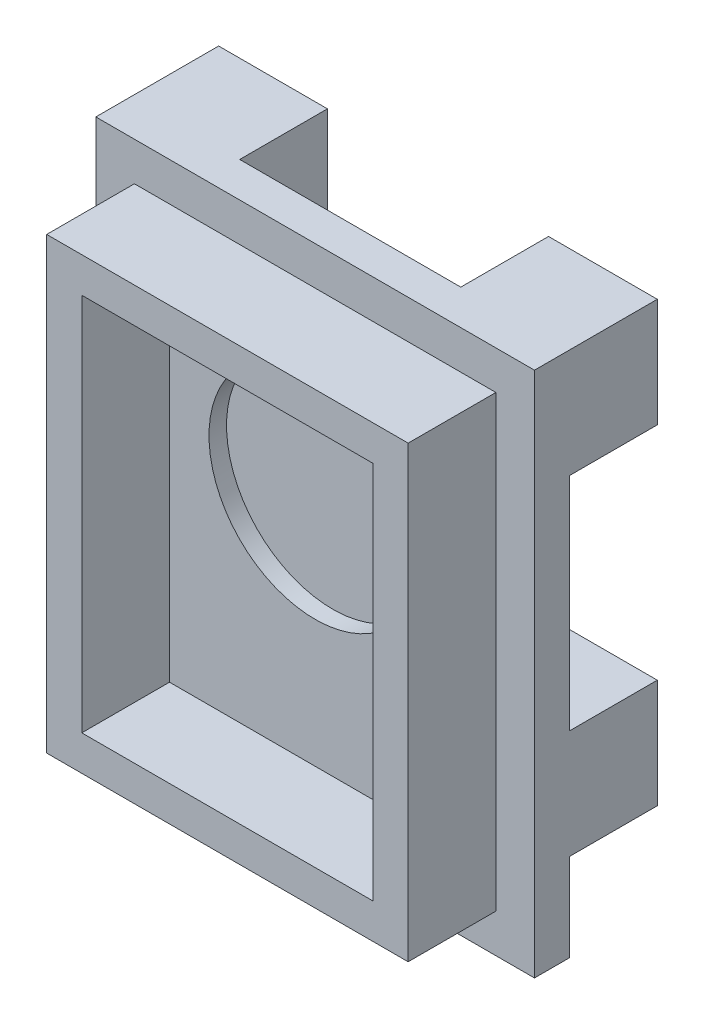
SolidWorks part; units mm, degrees
ref_plane "正面" through (0, 0, 0) normal (0, 0, 1) x (1, 0, 0)
ref_plane "平面" through (0, 0, 0) normal (0, 1, 0) x (1, 0, 0)
ref_plane "右側面" through (0, 0, 0) normal (1, 0, 0) x (0, 0, -1)
sketch "ｽｹｯﾁ1" plane through (0, 0, 0) normal (0, 0, 1) x (1, 0, 0)
  line L1 (-36.7373, 39.7071) -> (-11.7373, 39.7071)
  line L2 (-36.7373, 39.7071) -> (-36.7373, 9.7071)
  line L3 (-36.7373, 9.7071) -> (-11.7373, 9.7071)
  line L4 (-11.7373, 39.7071) -> (-11.7373, 9.7071)
  dimension "D3" = 25
  dimension "D4" = 30
extrude "ﾎﾞｽ - 押し出し1" add sketch "ｽｹｯﾁ1" along normal blind 2
sketch "ｽｹｯﾁ2" plane through (0, 0, 2) normal (0, 0, 1) x (1, 0, 0)
  line L0 (-11.7373, 39.7071) -> (-36.7373, 39.7071) construction
  line L1 (-13.9373, 37.5071) -> (-34.5373, 37.5071)
  line L2 (-13.9373, 37.5071) -> (-13.9373, 11.9071)
  line L3 (-13.9373, 11.9071) -> (-34.5373, 11.9071)
  line L4 (-34.5373, 37.5071) -> (-34.5373, 11.9071)
  line L5 (-36.7373, 9.7071) -> (-11.7373, 9.7071) construction
  line L6 (-36.7373, 39.7071) -> (-36.7373, 9.7071) construction
  line L7 (-11.7373, 9.7071) -> (-11.7373, 39.7071) construction
  dimension "D2" = 2.2
  dimension "D3" = 2.2
  dimension "D4" = 2.2
  dimension "D5" = 2.2
extrude "ﾎﾞｽ - 押し出し2" add sketch "ｽｹｯﾁ2" along normal blind 5
sketch "ｽｹｯﾁ3" plane through (0, 0, 7) normal (0, 0, 1) x (1, 0, 0)
  line L0 (-13.9373, 37.5071) -> (-34.5373, 37.5071) construction
  line L1 (-32.5373, 13.9071) -> (-15.9373, 13.9071)
  line L2 (-32.5373, 13.9071) -> (-32.5373, 35.5071)
  line L3 (-32.5373, 35.5071) -> (-15.9373, 35.5071)
  line L4 (-15.9373, 13.9071) -> (-15.9373, 35.5071)
  line L5 (-34.5373, 11.9071) -> (-13.9373, 11.9071) construction
  line L6 (-13.9373, 11.9071) -> (-13.9373, 37.5071) construction
  line L7 (-34.5373, 37.5071) -> (-34.5373, 11.9071) construction
  dimension "D1" = 21.6
  dimension "D2" = 16.6
  dimension "D3" = 2
  dimension "D4" = 2
  dimension "D5" = 2
  dimension "D6" = 2
extrude "ｶｯﾄ - 押し出し1" cut sketch "ｽｹｯﾁ3" against normal blind 5
sketch "ｽｹｯﾁ4" plane through (0, 0, 0) normal (0, 0, -1) x (-1, 0, 0)
  line L0 (11.7373, 39.7071) -> (36.7373, 39.7071) construction
  line L1 (11.7373, 39.7071) -> (17.9373, 39.7071)
  line L2 (11.7373, 39.7071) -> (11.7373, 33.5071)
  line L3 (11.7373, 33.5071) -> (17.9373, 33.5071)
  line L4 (17.9373, 39.7071) -> (17.9373, 33.5071)
  line L5 (36.7373, 39.7071) -> (30.5373, 39.7071)
  line L6 (36.7373, 39.7071) -> (36.7373, 33.5071)
  line L7 (36.7373, 33.5071) -> (30.5373, 33.5071)
  line L8 (30.5373, 39.7071) -> (30.5373, 33.5071)
  line L9 (36.7373, 14.7071) -> (30.5373, 14.7071)
  line L10 (36.7373, 14.7071) -> (36.7373, 20.9071)
  line L11 (36.7373, 20.9071) -> (30.5373, 20.9071)
  line L12 (30.5373, 14.7071) -> (30.5373, 20.9071)
  line L13 (11.7373, 14.7071) -> (17.9373, 14.7071)
  line L14 (11.7373, 14.7071) -> (11.7373, 20.9071)
  line L15 (11.7373, 20.9071) -> (17.9373, 20.9071)
  line L16 (17.9373, 14.7071) -> (17.9373, 20.9071)
  line L17 (36.7373, 39.7071) -> (36.7373, 9.7071) construction
  dimension "D1" = 6.2
  dimension "D2" = 6.2
  dimension "D3" = 6.2
  dimension "D4" = 6.2
  dimension "D5" = 6.2
  dimension "D6" = 6.2
  dimension "D7" = 6.2
  dimension "D8" = 25
  dimension "D9" = 25
sketch "ｽｹｯﾁ5" plane through (0, 0, 2) normal (0, 0, 1) x (1, 0, 0)
  line L0 (-36.7373, 39.7071) -> (-36.7373, 9.7071) construction
  line L1 (-11.7373, 39.7071) -> (-36.7373, 39.7071) construction
  circle A0 centre (-24.2373, 27.2071) radius 6.05
  dimension "D1" = 12.1
  dimension "D2" = 12.5
  dimension "D3" = 12.5
extrude "ｶｯﾄ - 押し出し3" cut sketch "ｽｹｯﾁ5" against normal blind 1
extrude "ﾎﾞｽ - 押し出し4" add sketch "ｽｹｯﾁ4" along normal blind 5
sketch "ｽｹｯﾁ6" plane through (0, 0, -5) normal (0, 0, -1) x (-1, 0, 0)
  line L0 (17.9373, 39.7071) -> (11.7373, 39.7071) construction
  line L1 (11.7373, 39.7071) -> (11.7373, 33.5071) construction
  line L2 (36.7373, 33.5071) -> (36.7373, 39.7071) construction
  line L3 (36.7373, 39.7071) -> (30.5373, 39.7071) construction
  line L4 (36.7373, 14.7071) -> (36.7373, 20.9071) construction
  line L5 (30.5373, 14.7071) -> (36.7373, 14.7071) construction
  line L6 (11.7373, 14.7071) -> (17.9373, 14.7071) construction
  line L7 (11.7373, 20.9071) -> (11.7373, 14.7071) construction
  circle A0 centre (14.7373, 36.7071) radius 1.4
  circle A1 centre (14.7373, 17.7071) radius 1.4
  circle A2 centre (33.7373, 36.7071) radius 1.4
  circle A3 centre (33.7373, 17.7071) radius 1.4
  dimension "D1" = 3
  dimension "D3" = 3
  dimension "D5" = 3
  dimension "D7" = 3
  dimension "D9" = 2.8
  dimension "D10" = 2.8
  dimension "D11" = 2.8
  dimension "D12" = 2.8
  dimension "D2" = 3
  dimension "D4" = 3
  dimension "D6" = 3
  dimension "D8" = 3
extrude "ｶｯﾄ - 押し出し5" cut sketch "ｽｹｯﾁ6" against normal blind 6
